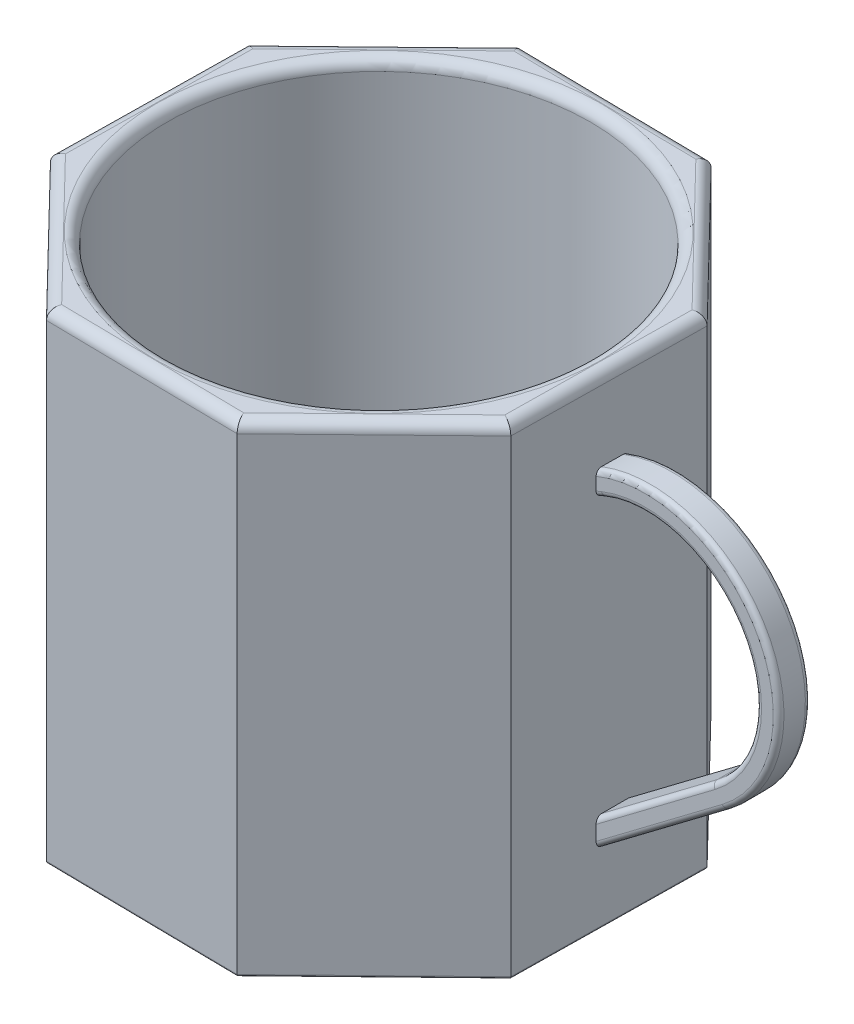
SolidWorks part; units mm, degrees
ref_plane "Front Plane" through (0, 0, 0) normal (0, 0, 1) x (1, 0, 0)
ref_plane "Top Plane" through (0, 0, 0) normal (0, 1, 0) x (1, 0, 0)
ref_plane "Right Plane" through (0, 0, 0) normal (1, 0, 0) x (0, 0, -1)
sketch "Sketch1" plane through (0, 0, 0) normal (0, 1, 0) x (1, 0, 0)
  line L1 (8.7328, -21.98) -> (21.7172, -9.3672)
  line L2 (21.7172, -9.3672) -> (21.98, 8.7328)
  line L3 (21.98, 8.7328) -> (9.3672, 21.7172)
  line L4 (9.3672, 21.7172) -> (-8.7328, 21.98)
  line L5 (-8.7328, 21.98) -> (-21.7172, 9.3672)
  line L6 (-21.7172, 9.3672) -> (-21.98, -8.7328)
  line L7 (-21.98, -8.7328) -> (-9.3672, -21.7172)
  line L8 (-9.3672, -21.7172) -> (8.7328, -21.98)
  dimension "D1" = 18.1
extrude "Boss-Extrude1" add sketch "Sketch1" along normal blind 45
sketch "Sketch2" plane through (0, 45, 0) normal (0, 1, 0) x (1, 0, 0)
  circle A0 centre (0, 0) radius 19.8
  dimension "D1" = 39.6
extrude "Cut-Extrude1" cut sketch "Sketch2" against normal blind 42
sketch "Sketch3" plane through (0, 0, 0) normal (0, -1, 0) x (1, 0, 0)
  circle A0 centre (0, 0) radius 19.8
  dimension "D1" = 39.6
extrude "Cut-Extrude2" cut sketch "Sketch3" against normal blind 1.5
fillet "Fillet1" radius 1 1 edges at (0, 0, -19.8)
fillet "Fillet2" radius 0.5 1 edges at (0, 1.5, -19.8)
fillet "Fillet3" radius 1 8 edges at (-15.6736, 45, 15.225) (-21.8486, 45, -0.3172) (-15.225, 45, -15.6736) (0.3172, 45, -21.8486) (15.6736, 45, -15.225) (21.8486, 45, 0.3172) (15.225, 45, 15.6736) (-0.3172, 45, 21.8486)
fillet "Fillet4" radius 1 1 edges at (0, 45, 19.8)
ref_plane "Plane1" through (0, 0, 0) normal (0, 0, 1) x (1, 0, 0)
sketch "Sketch4" plane through (0, 0, 0) normal (0, 0, 1) x (1, 0, 0)
  line L0 (21.7172, 6.5754) -> (33.9338, 15.7866)
  line L1 (21.7172, 44) -> (21.7172, 0) construction
  line L2 (20.453, 8.2521) -> (32.6695, 17.4633)
  line L3 (20.8935, 36.9704) -> (21.4906, 34.9634)
  arc A0 (33.9338, 15.7866) -> (21.7172, 37.3538) centre (26.4083, 25.7674) ccw
  arc A1 (32.6695, 17.4633) -> (22.5053, 35.4073) centre (26.4083, 25.7674) ccw
  arc A3 (20.453, 8.2521) -> (21.7172, 6.5754) centre (21.0851, 7.4137) ccw
  arc A4 (22.5053, 35.4073) -> (21.4906, 34.9634) centre (30.0286, 16.8255) ccw
  arc A5 (21.7172, 37.3538) -> (20.8935, 36.9704) centre (25.0679, 29.078) ccw
  dimension "D2" = 12.5
  dimension "D1" = 15.3
  dimension "D3" = 2.1
extrude "Boss-Extrude2" add sketch "Sketch4" along normal mid plane 3
fillet "Fillet5" radius 0.2 8 edges at (15.225, 0, 15.6736) (21.8486, 0, 0.3172) (15.6736, 0, -15.225) (0.3172, 0, -21.8486) (-15.225, 0, -15.6736) (-21.8486, 0, -0.3172) (-15.6736, 0, 15.225) (-0.3172, 0, 21.8486)
fillet "Fillet6" radius 0.5 4 edges at (27.8826, 11.224, 1.5) (27.9044, 11.2404, -1.5) (37.3148, 31.8746, 1.5) (37.3262, 31.8542, -1.5)
fillet "Fillet7" radius 0.5 3 edges at (27.2505, 13.3774, 1.5) (35.4574, 30.8932, 1.5) (22.1671, 35.2667, 1.5)
